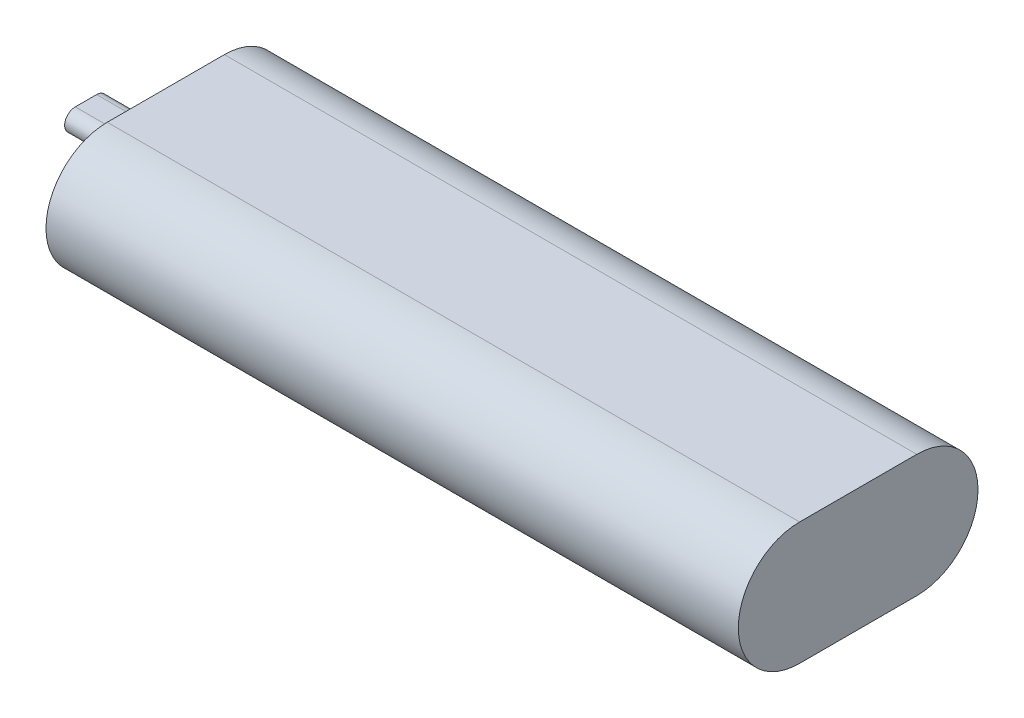
SolidWorks part; units mm, degrees
ref_plane "Front Plane" through (0, 0, 0) normal (0, 0, 1) x (1, 0, 0)
ref_plane "Top Plane" through (0, 0, 0) normal (0, 1, 0) x (1, 0, 0)
ref_plane "Right Plane" through (0, 0, 0) normal (1, 0, 0) x (0, 0, -1)
sketch "Sketch1" plane through (0, 0, 0) normal (1, 0, 0) x (0, 0, -1)
  line L0 (0, 0) -> (50000, 0) construction
  line L1 (-22.5, 7.8168) -> (-22.5, -49992.1832) construction
  line L2 (22.5, 10.7697) -> (22.5, -49989.2303) construction
  line L7 (-11, 0) -> (11, 0) construction
  line L8 (-11, 11.5) -> (11, 11.5)
  line L9 (-11, -11.5) -> (11, -11.5)
  arc A0 (-11, 11.5) -> (-11, -11.5) centre (-11, 0) ccw
  arc A1 (11, -11.5) -> (11, 11.5) centre (11, 0) ccw
  point P0 (0, 0)
  point P10 (0, 0)
  dimension "D1" = 45
  dimension "D2" = 23
extrude "Boss-Extrude1" add sketch "Sketch1" along normal blind 65 and the other way blind 65
sketch "Sketch2" plane through (-65, 0, 0) normal (-1, 0, 0) x (0, 0, 1)
  line L0 (-2, 0) -> (2, 0) construction
  line L1 (-2, 2) -> (2, 2)
  line L2 (-2, -2) -> (2, -2)
  line L3 (0, 0) -> (0, 50000) construction
  line L4 (0, 0) -> (50000, 0) construction
  arc A0 (-2, 2) -> (-2, -2) centre (-2, 0) ccw
  arc A1 (2, -2) -> (2, 2) centre (2, 0) ccw
  point P3 (0, 0)
  dimension "D2" = 2
  dimension "D1" = 4
extrude "Boss-Extrude2" add sketch "Sketch2" along normal blind 15
